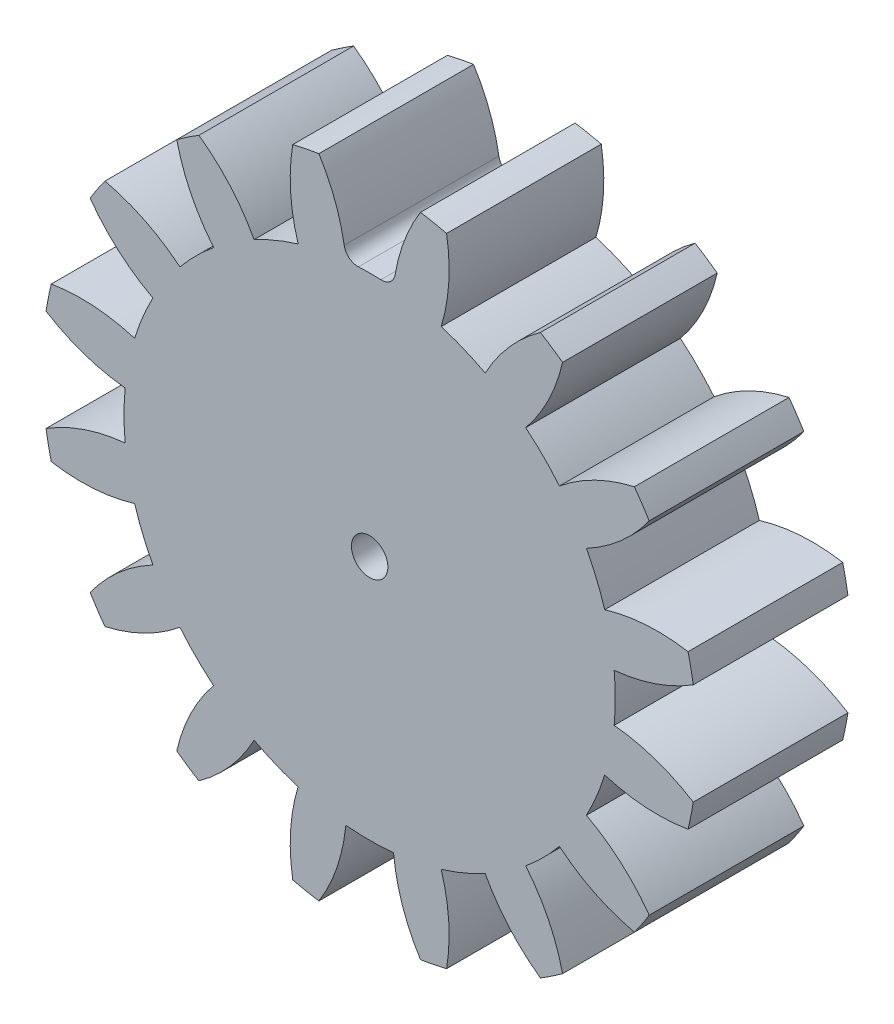
SolidWorks part; units mm, degrees
ref_plane "Front Plane" through (0, 0, 0) normal (0, 0, 1) x (1, 0, 0)
ref_plane "Top Plane" through (0, 0, 0) normal (0, 1, 0) x (1, 0, 0)
ref_plane "Right Plane" through (0, 0, 0) normal (1, 0, 0) x (0, 0, -1)
sketch "Sketch1" plane through (0, 0, 0) normal (0, 0, 1) x (1, 0, 0)
  circle A0 centre (0, 0) radius 18
  circle A1 centre (0, 0) radius 1
  dimension "D1" = 2
  dimension "D2" = 36
extrude "Boss-Extrude1" add sketch "Sketch1" along normal mid plane 8.5
sketch "Sketch2" plane through (0, 0, 0) normal (0, 0, 1) x (1, 0, 0)
  line L0 (0, 0) -> (0, 18) construction
  line L1 (0, 0) -> (-1.3096, 13.4363) construction
  line L2 (0, 10.7625) -> (-3.5688, 20.5678) construction
  arc A0 (1.8665, 15.8908) -> (-1.8665, 15.8908) centre (0, 0) ccw construction
  arc A1 (1.3096, 13.4363) -> (-1.3096, 13.4363) centre (0, 0) ccw
  circle A2 centre (0, 0) radius 18 construction
  arc A3 (2.7904, 17.7824) -> (-2.7904, 17.7824) centre (0, 0) ccw
  arc A4 (-1.3096, 13.4363) -> (-2.7904, 17.7824) centre (-11.2801, 12.4645) ccw
  arc A5 (1.3096, 13.4363) -> (2.7904, 17.7824) centre (11.2801, 12.4645) cw
  dimension "D1" = 32
  dimension "D2" = 4.5
  dimension "D3" = 20
  dimension "D4" = 3.7416
extrude "Cut-Extrude1" cut sketch "Sketch2" against normal through all both and the other way through all
fillet "Fillet1" radius 0.76 2 edges at (1.3096, 13.4363, 0) (-1.3096, 13.4363, 0)
pattern_circular "CirPattern3" count 16 over 360 about axis through (0, 0, 4.25) along (0, 0, -1) of "Cut-Extrude1"
equation "\"Module\"= 2"
equation "\"Pressure Angle\"= 20"
equation "\"Bore\"= 2"
equation "\"NumTeeth\"= 16"
equation "\"D1@Sketch1\"=\"Bore\""
equation "\"D2@Sketch1\"=(\"NumTeeth\"+2)*\"Module\""
equation "\"D1@Sketch2\"=\"NumTeeth\"*\"Module\""
equation "\"ToothDepth\"= IIF ( \"Module\" < 1.25 , 2.4 * \"Module\" , 2.25 * \"Module\" )"
equation "\"D2@Sketch2\"=\"ToothDepth\""
equation "\"D3@Sketch2\"=\"Pressure Angle\""
equation "\"D4@Sketch2\"=((\"Module\"*PI)/2)+0.3*\"Module\""
equation "\"D1@Fillet1\"=\"Module\"*0.38"
equation "\"D1@CirPattern3\"=\"NumTeeth\""
